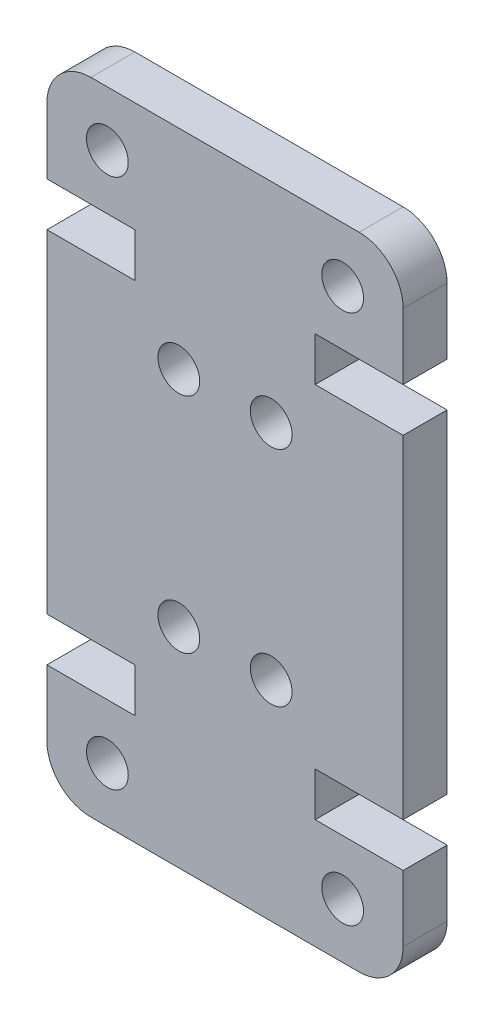
SolidWorks part; units mm, degrees
ref_plane "Front Plane" through (0, 0, 0) normal (0, 0, 1) x (1, 0, 0)
ref_plane "Top Plane" through (0, 0, 0) normal (0, 1, 0) x (1, 0, 0)
ref_plane "Right Plane" through (0, 0, 0) normal (1, 0, 0) x (0, 0, -1)
sketch "Sketch1" plane through (0, 0, 0) normal (0, 0, 1) x (1, 0, 0)
  line L0 (0, 22.14) -> (0, 7)
  line L1 (16.2, 2) -> (16.2, 5)
  line L2 (12.2, 5) -> (16.2, 5)
  line L3 (2, 0) -> (14.2, 0)
  line L4 (16.2, 7) -> (12.2, 7)
  line L5 (12.2, 7) -> (12.2, 5)
  line L6 (16.2, 22.14) -> (16.2, 7)
  line L7 (4, 7) -> (4, 5)
  line L8 (0, 27.14) -> (0, 24.14)
  line L9 (4, 24.14) -> (0, 24.14)
  line L10 (0, 7) -> (4, 7)
  line L11 (0, 22.14) -> (4, 22.14)
  line L12 (4, 5) -> (0, 5)
  line L13 (4, 22.14) -> (4, 24.14)
  line L14 (12.2, 22.14) -> (12.2, 24.14)
  line L15 (16.2, 22.14) -> (12.2, 22.14)
  line L16 (0, 2) -> (0, 5)
  line L17 (2, 29.14) -> (14.2, 29.14)
  line L18 (12.2, 24.14) -> (16.2, 24.14)
  line L19 (16.2, 27.14) -> (16.2, 24.14)
  line L20 (8.1, 29.14) -> (8.1, 0) construction
  line L21 (0, 14.57) -> (16.2, 14.57) construction
  circle A0 centre (13.45, 2.5) radius 0.95
  circle A1 centre (10.2, 9.5) radius 0.95
  arc A2 (16.2, 2) -> (14.2, 0) centre (14.2, 2) cw
  circle A3 centre (2.75, 26.64) radius 0.95
  circle A4 centre (6, 19.64) radius 0.95
  arc A5 (0, 2) -> (2, 0) centre (2, 2) ccw
  arc A6 (0, 27.14) -> (2, 29.14) centre (2, 27.14) cw
  circle A7 centre (6, 9.5) radius 0.95
  arc A8 (16.2, 27.14) -> (14.2, 29.14) centre (14.2, 27.14) ccw
  circle A9 centre (2.75, 2.5) radius 0.95
  circle A10 centre (10.2, 19.64) radius 0.95
  circle A11 centre (13.45, 26.64) radius 0.95
  point P15 (8.1, 14.57)
  dimension "D1" = 1.9
  dimension "D2" = 2
  dimension "D3" = 2.75
  dimension "D4" = 6
  dimension "D5" = 8.1
  dimension "D6" = 2.5
  dimension "D9" = 9.5
  dimension "D10" = 14.57
  dimension "D7" = 5
extrude "Boss-Extrude1" add sketch "Sketch1" along normal blind 2
equation "\"D5@Sketch1\"= \"fingerWidth@parametersSketch@prostheticParameters.SLDPRT\" / 2'PIP width"
equation "\"D10@Sketch1\"= ( \"HL@parametersSketch@prostheticParameters.SLDPRT\" * 0.244 - 4 - 12 ) / 2 'PIP length - Sil.Sht PIP - Sil. Sht MIP"
equation "\"D1@Sketch1\"= 1.5 + \"tol1@parametersSketch@prostheticParameters.SLDPRT\""
